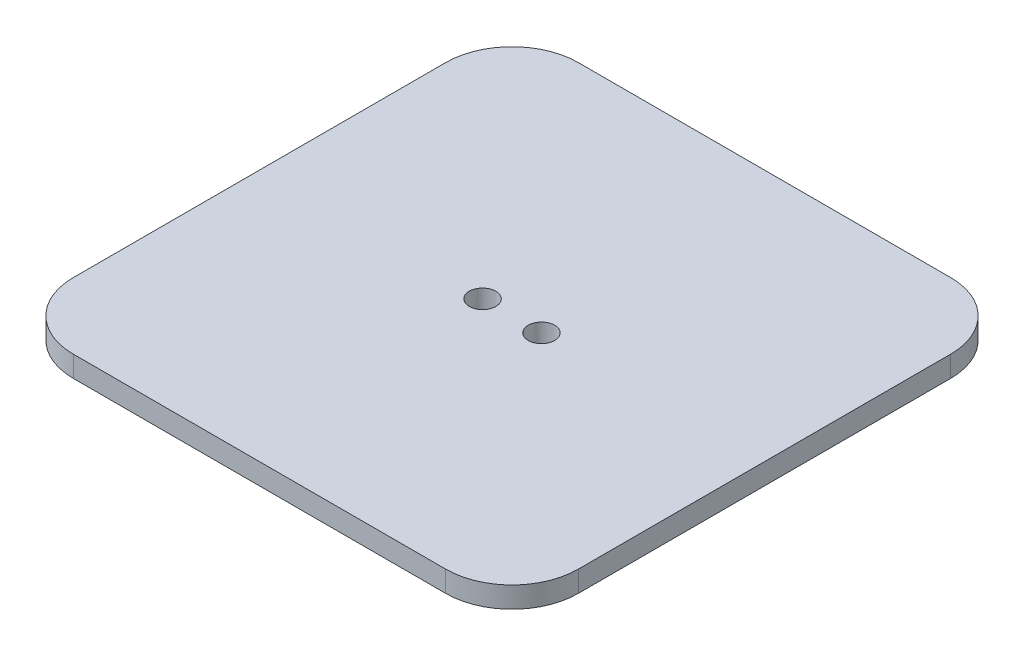
SolidWorks part; units mm, degrees
ref_plane "Front Plane" through (0, 0, 0) normal (0, 0, 1) x (1, 0, 0)
ref_plane "Top Plane" through (0, 0, 0) normal (0, 1, 0) x (1, 0, 0)
ref_plane "Right Plane" through (0, 0, 0) normal (1, 0, 0) x (0, 0, -1)
sketch "Sketch1" plane through (0, 0, 0) normal (0, 1, 0) x (1, 0, 0)
  line L1 (-38.1, -38.1) -> (38.1, -38.1)
  line L2 (-38.1, -38.1) -> (-38.1, 38.1)
  line L3 (-38.1, 38.1) -> (38.1, 38.1)
  line L4 (38.1, -38.1) -> (38.1, 38.1)
  line L5 (-38.1, -38.1) -> (38.1, 38.1) construction
  line L6 (-38.1, 38.1) -> (38.1, -38.1) construction
  point P0 (0, 0)
  dimension "D1" = 76.2
  dimension "D2" = 76.2
extrude "Boss-Extrude1" add sketch "Sketch1" along normal blind 3.175
fillet "Fillet1" radius 10 1 edges at (-38.1, 1.5875, 38.1)
fillet "Fillet2" radius 10 1 edges at (-38.1, 1.5875, -38.1)
fillet "Fillet3" radius 10 1 edges at (38.1, 1.5875, -38.1)
fillet "Fillet4" radius 10 1 edges at (38.1, 1.5875, 38.1)
sketch "Sketch2" plane through (0, 3.175, 0) normal (0, 1, 0) x (1, 0, 0)
  line L0 (-1.7463, 0) -> (1.7463, 0) construction
  circle A0 centre (4.445, 0) radius 2
  circle A1 centre (-4.445, 0) radius 2
  dimension "D1" = 4
  dimension "D2" = 4
  dimension "D3" = 8.89
  dimension "D4" = 4.445
extrude "Cut-Extrude1" cut sketch "Sketch2" against normal through all
ref_axis "Axis1" through (0, -0.1588, 0) along (0, 1, 0)
